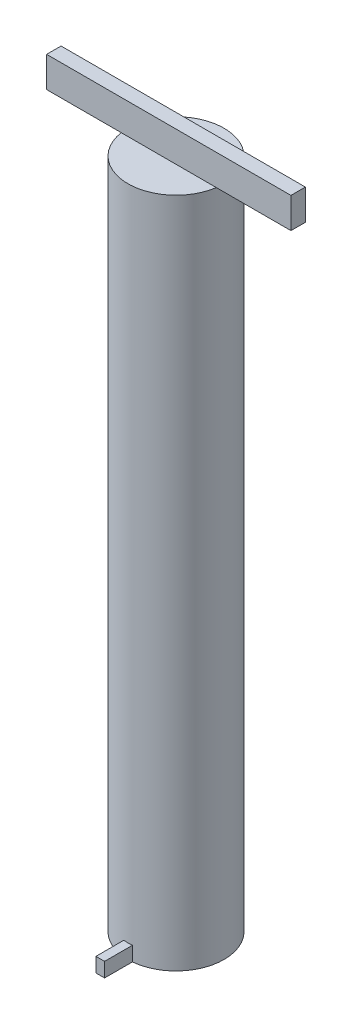
SolidWorks part; units mm, degrees
ref_plane "Front Plane" through (0, 0, 0) normal (0, 0, 1) x (1, 0, 0)
ref_plane "Top Plane" through (0, 0, 0) normal (0, 1, 0) x (1, 0, 0)
ref_plane "Right Plane" through (0, 0, 0) normal (1, 0, 0) x (0, 0, -1)
sketch "Sketch1" plane through (0, 0, 0) normal (0, 1, 0) x (1, 0, 0)
  circle A0 centre (0, 0) radius 10
  dimension "D1" = 20
extrude "Boss-Extrude1" add sketch "Sketch1" along normal blind 139.7
sketch "Sketch3" plane through (0, 0, 0) normal (0, -1, 0) x (1, 0, 0)
  line L1 (-0.9, 15.75) -> (0.9, 15.75)
  line L2 (-0.9, 15.75) -> (-0.9, 9.3548)
  line L4 (0.9, 15.75) -> (0.9, 9.3548)
  arc A0 (0.9, 9.3548) -> (-0.9, 9.3548) centre (0, 0) ccw
  dimension "D1" = 0.9
  dimension "D3" = 15.75
extrude "Boss-Extrude2" add sketch "Sketch3" against normal blind 3
sketch "Sketch4" plane through (0, 139.7, 0) normal (0, 1, 0) x (1, 0, 0)
  line L1 (-25.4, 1.5) -> (25.4, 1.5)
  line L2 (-25.4, 1.5) -> (-25.4, -1.5)
  line L3 (-25.4, -1.5) -> (25.4, -1.5)
  line L4 (25.4, 1.5) -> (25.4, -1.5)
  point P4 (-25.4, 0)
  point P5 (0, 1.5)
  dimension "D1" = 50.8
  dimension "D2" = 3
extrude "Boss-Extrude3" add sketch "Sketch4" along normal blind 6.35
sketch "Sketch5" plane through (0, 0, 0) normal (0, -1, 0) x (1, 0, 0)
  circle A0 centre (0, 0) radius 6.25
  dimension "D1" = 12.5
extrude "Cut-Extrude1" cut sketch "Sketch5" against normal blind 4
